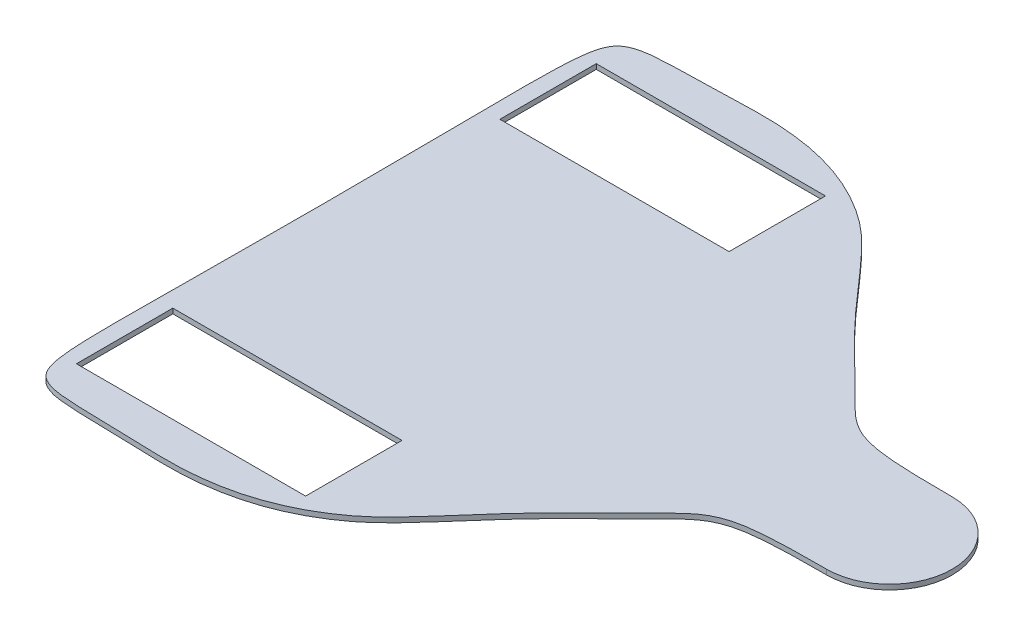
SolidWorks part; units mm, degrees
material "PLA"
ref_plane "Front Plane" through (0, 0, 0) normal (0, 0, 1) x (1, 0, 0)
ref_plane "Top Plane" through (0, 0, 0) normal (0, 1, 0) x (1, 0, 0)
ref_plane "Right Plane" through (0, 0, 0) normal (1, 0, 0) x (0, 0, -1)
sketch "base dimensions" plane through (0, 0, 0) normal (0, 1, 0) x (1, 0, 0)
  line L0 (0, 0) -> (-116.6267, 0) construction
  line L2 (-112.85, 41.1) -> (-112.85, -41.1)
  line L3 (-96.85, 41.1) -> (-96.85, -41.1)
  line L5 (-112.85, 41.1) -> (-96.85, -41.1) construction
  line L6 (-96.85, 41.1) -> (-112.85, -41.1) construction
  line L7 (-131.85, -27.5) -> (-114.85, -27.5)
  line L8 (-131.85, -27.5) -> (-131.85, 27.5)
  line L9 (-114.85, -27.5) -> (-114.85, 27.5)
  line L10 (-131.85, 27.5) -> (-114.85, 27.5)
  line L11 (-131.85, -27.5) -> (-114.85, 27.5) construction
  line L12 (-114.85, -27.5) -> (-131.85, 27.5) construction
  line L13 (-94.85, 0) -> (-94.85, 10.9056)
  line L14 (-135.85, -577.028) -> (-135.85, 577.028) construction
  line L16 (-130.25, -60.15) -> (-79.45, -60.15)
  line L17 (-130.25, 41.1) -> (-79.45, 41.1)
  line L18 (-130.25, 41.1) -> (-130.25, 60.15)
  line L19 (-130.25, 60.15) -> (-79.45, 60.15)
  line L20 (-79.45, 41.1) -> (-79.45, 60.15)
  line L21 (-79.45, -41.1) -> (-79.45, -60.15)
  line L22 (-130.25, -41.1) -> (-79.45, -41.1)
  line L23 (-130.25, -41.1) -> (-130.25, -60.15)
  circle A0 centre (0, 0) radius 63.5 construction
  circle A1 centre (0, 0) radius 15
  circle A2 centre (-81, 0) radius 13.85
  spline S0 degree 3 poles (0, 15) (-26.0597, 15) (-24.2984, 16.8762) (-51.0086, 41.9815) (-61.2896, 55.9447) (-79.9531, 69.6921) (-95.0158, 71.7163) (-110.819, 71.0052) (-126.522, 70.8741) (-138.1428, 68.2179) (-135.85, 61.1511) (-135.85, 0) knots 0 0 0 0 0.141138 0.170317 0.278296 0.317035 0.518967 0.554463 0.636493 0.682072 1 1 1 1
  spline S1 degree 3 poles (0, -15) (-26.0597, -15) (-24.2984, -16.8762) (-51.0086, -41.9815) (-61.2896, -55.9447) (-79.9531, -69.6921) (-95.0158, -71.7163) (-110.819, -71.0052) (-126.522, -70.8741) (-138.1428, -68.2179) (-135.85, -61.1511) (-135.85, 0) knots 0 0 0 0 0.141138 0.170317 0.278296 0.317035 0.518967 0.554463 0.636493 0.682072 1 1 1 1
  point P4 (-96.85, 0)
  point P8 (-67.15, 0)
  point P10 (-104.85, 0)
  point P11 (-63.5, 0)
  point P20 (-123.35, 0)
  point P27 (-114.85, 0)
  dimension "D1" = 127
  dimension "D2" = 30
  dimension "D5" = 27.7
  dimension "D9" = 2
  dimension "D10" = 81
  dimension "D15" = 90
  dimension "D3" = 82.2
  dimension "D4" = 16
  dimension "D6" = 55
  dimension "D7" = 17
  dimension "D8" = 2
  dimension "D11" = 19.05
  dimension "D12" = 50.8
  dimension "D14" = 3.65
  dimension "D18" = 4
extrude "Boss-Extrude1" add sketch "base dimensions" against normal blind 1.2 contours S1 A1 S0 L23 L22 L2 L17 L18 L19 L20 L3 L21 L16 A2 L8 L10 L9 L7 | L22 L23 L16 L21 | L2 L22 L3 L17 | L10 L8 L7 L9 | L17 L20 L19 L18 | A2 | A1 region at (-104.85, 0, 0) region at (-104.85, 0, -50.625) region at (-104.85, 0, 50.625) region at (-123.35, 0, 0) region at (0, 0, 0) region at (-16.9714, 0, 0) region at (-81, 0, 0)
sketch "Sketch2" plane through (0, -1.2, 0) normal (0, -1, 0) x (-1, 0, 0)
  line L4 (-200000, 0) -> (200116.6267, 0) construction
  line L5 (-200000, 0) -> (200116.6267, 0)
  line L8 (132.25, 39.1) -> (132.25, 62.15)
  line L9 (77.45, 39.1) -> (132.25, 39.1)
  line L10 (77.45, 62.15) -> (77.45, 39.1)
  line L11 (132.25, 62.15) -> (77.45, 62.15)
  line L12 (132.25, 39.1) -> (132.25, 62.15)
  line L13 (77.45, 39.1) -> (132.25, 39.1)
  line L14 (77.45, 62.15) -> (77.45, 39.1)
  line L15 (132.25, 62.15) -> (77.45, 62.15)
  line L22 (77.45, -62.15) -> (132.25, -62.15)
  line L23 (77.45, -39.1) -> (77.45, -62.15)
  line L24 (132.25, -39.1) -> (77.45, -39.1)
  line L25 (132.25, -62.15) -> (132.25, -39.1)
  line L26 (77.45, -62.15) -> (132.25, -62.15)
  line L27 (77.45, -39.1) -> (77.45, -62.15)
  line L28 (132.25, -39.1) -> (77.45, -39.1)
  line L29 (132.25, -62.15) -> (132.25, -39.1)
  dimension "D1" = 2
  dimension "D2" = 2
extrude "Cut-Extrude1" cut sketch "Sketch2" against normal through all
